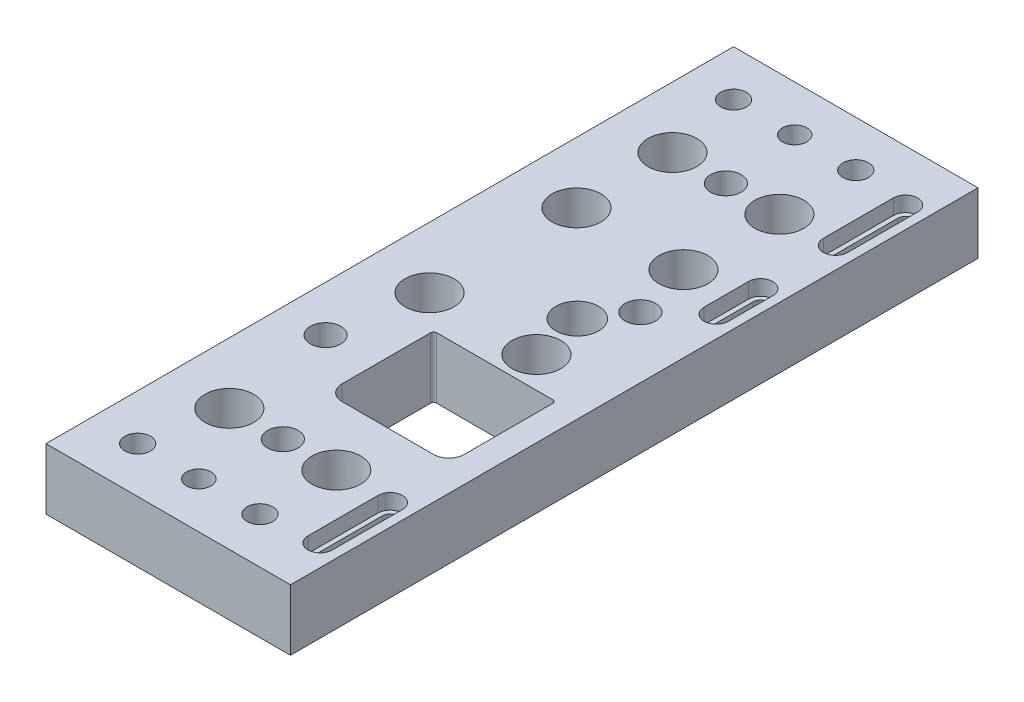
SolidWorks part; units mm, degrees
material "Plain Carbon Steel"
ref_plane "Front Plane" through (0, 0, 0) normal (0, 0, 1) x (1, 0, 0)
ref_plane "Top Plane" through (0, 0, 0) normal (0, 1, 0) x (1, 0, 0)
ref_plane "Right Plane" through (0, 0, 0) normal (1, 0, 0) x (0, 0, -1)
sketch "Sketch1" plane through (0, 0, 0) normal (0, 1, 0) x (1, 0, 0)
  line L1 (-40, -112.5) -> (40, -112.5)
  line L2 (-40, -112.5) -> (-40, 112.5)
  line L3 (-40, 112.5) -> (40, 112.5)
  line L4 (40, -112.5) -> (40, 112.5)
  line L5 (-40, -112.5) -> (40, 112.5) construction
  line L6 (-40, 112.5) -> (40, -112.5) construction
  point P0 (0, 0)
  dimension "D1" = 225
  dimension "D2" = 80
extrude "Boss-Extrude1" add sketch "Sketch1" against normal blind 20
sketch "Sketch2" plane through (0, 0, 0) normal (0, 1, 0) x (1, 0, 0)
  line L0 (23, -52.14) -> (26.5, -52.14) construction
  line L2 (31.5, -47.14) -> (31.5, -19.64) construction
  line L4 (31.5, -47.14) -> (31.5, -18.14)
  line L5 (-3.5, -52.14) -> (26.5, -52.14)
  line L6 (-8.5, -18.14) -> (-8.5, -47.14)
  line L7 (-7.5, -17.14) -> (30.5, -17.14)
  arc A2 (26.5, -52.14) -> (31.5, -47.14) centre (26.5, -47.14) ccw construction
  arc A5 (26.5, -52.14) -> (31.5, -47.14) centre (26.5, -47.14) ccw
  arc A6 (-8.5, -47.14) -> (-3.5, -52.14) centre (-3.5, -47.14) ccw
  arc A7 (30.5, -17.14) -> (31.5, -18.14) centre (30.5, -18.14) cw
  arc A8 (-7.5, -17.14) -> (-8.5, -18.14) centre (-7.5, -18.14) ccw
  dimension "D1" = 5
  dimension "D3" = 1
  dimension "D2" = 40
  dimension "D4" = 35
extrude "Cut-Extrude1" cut sketch "Sketch2" against normal up to next
sketch "Sketch3" plane through (0, 0, 0) normal (0, 1, 0) x (1, 0, 0)
  line L4 (35.5, -95.77) -> (35.5, -72.87)
  line L5 (30.5, -72.87) -> (30.5, -95.77)
  line L6 (35.5, -95.77) -> (35.5, -72.87)
  line L7 (30.5, -72.87) -> (30.5, -95.77)
  line L10 (35.5, 33.86) -> (35.5, 48.36)
  line L11 (30.5, 48.36) -> (30.5, 33.86)
  line L12 (35.5, 33.86) -> (35.5, 48.36)
  line L13 (30.5, 48.36) -> (30.5, 33.86)
  line L16 (35.5, 72.87) -> (35.5, 95.77)
  line L17 (30.5, 95.77) -> (30.5, 72.87)
  line L18 (35.5, 72.87) -> (35.5, 95.77)
  line L19 (30.5, 95.77) -> (30.5, 72.87)
  arc A4 (35.5, -72.87) -> (30.5, -72.87) centre (33, -72.87) ccw
  arc A5 (30.5, -95.77) -> (35.5, -95.77) centre (33, -95.77) ccw
  arc A6 (35.5, -72.87) -> (30.5, -72.87) centre (33, -72.87) ccw
  arc A7 (30.5, -95.77) -> (35.5, -95.77) centre (33, -95.77) ccw
  arc A10 (35.5, 48.36) -> (30.5, 48.36) centre (33, 48.36) ccw
  arc A11 (30.5, 33.86) -> (35.5, 33.86) centre (33, 33.86) ccw
  arc A12 (35.5, 48.36) -> (30.5, 48.36) centre (33, 48.36) ccw
  arc A13 (30.5, 33.86) -> (35.5, 33.86) centre (33, 33.86) ccw
  arc A16 (35.5, 95.77) -> (30.5, 95.77) centre (33, 95.77) ccw
  arc A17 (30.5, 72.87) -> (35.5, 72.87) centre (33, 72.87) ccw
  arc A18 (35.5, 95.77) -> (30.5, 95.77) centre (33, 95.77) ccw
  arc A19 (30.5, 72.87) -> (35.5, 72.87) centre (33, 72.87) ccw
  dimension "D1" = 0.05
  dimension "D2" = 0.05
  dimension "D3" = 0.05
extrude "Cut-Extrude2" cut sketch "Sketch3" against normal up to next
sketch "Sketch4" plane through (0, 0, 0) normal (0, 1, 0) x (1, 0, 0)
  line L4 (37, 72.87) -> (37, 95.77)
  line L5 (29, 95.77) -> (29, 72.87)
  line L6 (37, 72.87) -> (37, 95.77)
  line L7 (29, 95.77) -> (29, 72.87)
  line L10 (37, 33.86) -> (37, 48.36)
  line L11 (29, 48.36) -> (29, 33.86)
  line L12 (37, 33.86) -> (37, 48.36)
  line L13 (29, 48.36) -> (29, 33.86)
  line L16 (37, -95.77) -> (37, -72.87)
  line L17 (29, -72.87) -> (29, -95.77)
  line L18 (37, -95.77) -> (37, -72.87)
  line L19 (29, -72.87) -> (29, -95.77)
  arc A4 (37, 95.77) -> (29, 95.77) centre (33, 95.77) ccw
  arc A5 (29, 72.87) -> (37, 72.87) centre (33, 72.87) ccw
  arc A6 (37, 95.77) -> (29, 95.77) centre (33, 95.77) ccw
  arc A7 (29, 72.87) -> (37, 72.87) centre (33, 72.87) ccw
  arc A10 (37, 48.36) -> (29, 48.36) centre (33, 48.36) ccw
  arc A11 (29, 33.86) -> (37, 33.86) centre (33, 33.86) ccw
  arc A12 (37, 48.36) -> (29, 48.36) centre (33, 48.36) ccw
  arc A13 (29, 33.86) -> (37, 33.86) centre (33, 33.86) ccw
  arc A16 (37, -72.87) -> (29, -72.87) centre (33, -72.87) ccw
  arc A17 (29, -95.77) -> (37, -95.77) centre (33, -95.77) ccw
  arc A18 (37, -72.87) -> (29, -72.87) centre (33, -72.87) ccw
  arc A19 (29, -95.77) -> (37, -95.77) centre (33, -95.77) ccw
  dimension "D1" = 1.5
  dimension "D2" = 1.5
  dimension "D3" = 1.5
extrude "Cut-Extrude3" cut sketch "Sketch4" against normal blind 5
hole_wizard "CBORE for M8 Hex Socket Head Cap Screw1" positions "Sketch18" profile "Sketch8" counterbore size "M8" standard "ISO" end condition through all
sketch "Sketch18" plane through (0, -20, 0) normal (0, -1, 0) x (-1, 0, 0)
  line L0 (40, -112.5) -> (-40, -112.5) construction
  line L1 (-40, -112.5) -> (-40, 112.5) construction
  line L2 (40, 112.5) -> (40, -112.5) construction
  line L3 (-40, 112.5) -> (40, 112.5) construction
  point P0 (25, 97.5)
  point P2 (-15, 97.5)
  point P4 (-15, -97.5)
  point P6 (25, -97.5)
  dimension "D1" = 15
  dimension "D2" = 25
  dimension "D3" = 15
  dimension "D4" = 15
sketch "Sketch8" plane through (-25, -20, -97.5) normal (1, 0, 0) x (0, 0, -1)
  line L0 (0, 0) -> (0, 20)
  line L1 (0, 20) -> (4.2, 20)
  line L3 (4.2, 20) -> (4.2, 8.6)
  line L4 (7.5, 8.6) -> (4.2, 8.6)
  line L5 (7.5, 8.6) -> (7.5, 0.025)
  line L6 (7.5, 0.025) -> (7.525, 0)
  line L7 (7.525, 0) -> (0, 0)
  line L8 (-7.5, 0.025) -> (-7.525, 0) construction
  line L11 (0, -6.35) -> (0, 107.95) construction
  dimension "Thru Hole Dia." = 8.4
  dimension "Thru Hole Depth" = 20
  dimension "C'Bore Dia." = 15
  dimension "C'Bore Depth" = 8.6
  dimension "Near C'Sink Dia." = 15.05
  dimension "Near C'Sink Angle" = 90
hole_wizard "Ø8.0mm Dowel Hole1" positions "Sketch12" profile "Sketch11" hole size "Ø8.0" standard "ISO" end condition through all
sketch "Sketch12" plane through (0, -20, 0) normal (0, -1, 0) x (-1, 0, 0)
  line L0 (25, 97.5) -> (-15, 97.5) construction
  line L2 (25, -97.5) -> (-15, -97.5) construction
  point P0 (5, -97.5)
  point P2 (5, 97.5)
sketch "Sketch11" plane through (-5, -20, 97.5) normal (1, 0, 0) x (0, 0, -1)
  line L0 (0, 0) -> (0, 20)
  line L1 (0, 20) -> (4, 20)
  line L2 (4, 20) -> (4, 0.025)
  line L3 (4, 0.025) -> (4.025, 0)
  line L5 (4.025, 0) -> (0, 0)
  line L6 (-4, 0.025) -> (-4.025, 0) construction
  line L11 (0, -6.35) -> (0, 107.95) construction
  dimension "Thru Hole Dia." = 8
  dimension "Thru Hole Depth" = 20
  dimension "Near C'Sink Dia." = 8.05
  dimension "Near C'Sink Angle" = 90
sketch "Sketch13" plane through (0, 0, 0) normal (0, 1, 0) x (1, 0, 0)
  circle A0 centre (15, 41.11) radius 8 construction
  circle A1 centre (15, -7) radius 8 construction
  circle A2 centre (15, -72.5) radius 8 construction
  circle A3 centre (-20, -72.5) radius 8 construction
  circle A4 centre (-20, -7) radius 8 construction
  circle A5 centre (-20, 41.11) radius 8 construction
  circle A6 centre (-20, 72.5) radius 8 construction
  circle A7 centre (15, 72.5) radius 8 construction
  circle A8 centre (15, 41.11) radius 8
  circle A9 centre (15, -7) radius 8
  circle A10 centre (15, -72.5) radius 8
  circle A11 centre (-20, -72.5) radius 8
  circle A12 centre (-20, -7) radius 8
  circle A13 centre (-20, 41.11) radius 8
  circle A14 centre (-20, 72.5) radius 8
  circle A15 centre (15, 72.5) radius 8
extrude "Cut-Extrude4" cut sketch "Sketch13" against normal up to next
sketch "Sketch15" plane through (0, 0, 0) normal (0, 1, 0) x (1, 0, 0)
  circle A0 centre (-2.5, -72.5) radius 5
  circle A1 centre (-25, -36) radius 5
  circle A2 centre (20, 22) radius 5
  circle A3 centre (-2.5, 72.5) radius 5
  dimension "D1" = 10
extrude "Cut-Extrude5" cut sketch "Sketch15" against normal up to next
sketch "Sketch17" plane through (0, 0, 0) normal (0, 1, 0) x (1, 0, 0)
  circle A0 centre (11.5, 9.86) radius 7
  dimension "D1" = 14
extrude "Cut-Extrude6" cut sketch "Sketch17" against normal up to next
